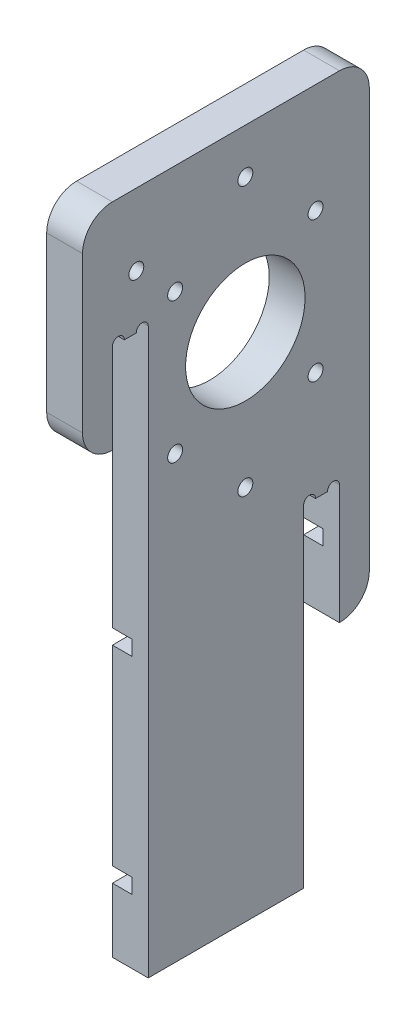
SolidWorks part; units mm, degrees
material "HDPE-green"
ref_plane "Front Plane" through (0, 0, 0) normal (0, 0, 1) x (1, 0, 0)
ref_plane "Top Plane" through (0, 0, 0) normal (0, 1, 0) x (1, 0, 0)
ref_plane "Right Plane" through (0, 0, 0) normal (1, 0, 0) x (0, 0, -1)
sketch "Sketch1" plane through (0, 0, 0) normal (1, 0, 0) x (0, 0, -1)
  line L1 (-31.5, 60) -> (31.5, 60)
  line L2 (-31.5, 60) -> (-31.5, -60)
  line L3 (-31.5, -60) -> (31.5, -60)
  line L4 (31.5, 60) -> (31.5, -60)
  line L5 (-31.5, 60) -> (31.5, -60) construction
  line L6 (-31.5, -60) -> (31.5, 60) construction
  circle A0 centre (0, 0) radius 20
  point P0 (0, 0)
  dimension "D3" = 40
  dimension "D1" = 63
  dimension "D2" = 120
extrude "Boss-Extrude1" add sketch "Sketch1" along normal blind 12
hole_wizard "Ø5.0 (5) Diameter Hole2" positions "Sketch5" profile "Sketch4" hole size "Ø5.0" standard "ISO" end condition up to next
sketch "Sketch5" plane through (0, 0, 0) normal (-1, 0, 0) x (0, 0, 1)
  point P0 (-23.5, 23.5)
  point P1 (23.5, 23.5)
  point P3 (23.5, -23.5)
  point P5 (-23.5, -23.5)
  dimension "D1" = 23.5
  dimension "D2" = 23.5
  dimension "D3" = 23.5
  dimension "D4" = 23.5
  dimension "D5" = 23.5
  dimension "D6" = 23.5
  dimension "D7" = 23.5
  dimension "D8" = 23.5
sketch "Sketch4" plane through (0, 23.5, -23.5) normal (0, 1, 0) x (0, 0, 1)
  line L0 (0, 0) -> (0, 12)
  line L1 (0, 12) -> (2.5, 12)
  line L2 (2.5, 12) -> (2.5, 0)
  line L5 (2.5, 0) -> (0, 0)
  line L11 (0, -6.35) -> (0, 107.95) construction
  dimension "Thru Hole Dia." = 5
  dimension "Thru Hole Depth" = 12
hole_wizard "Linear Rail Mount Hole" positions "Sketch7" profile "Sketch6" legacy end condition up to next
sketch "Sketch7" plane through (0, 0, 0) normal (-1, 0, 0) x (0, 0, 1)
  line L0 (0, -57.2998) -> (0, 35.7294) construction
  point P0 (0, 45)
  point P1 (0, -45)
  dimension "D1" = 45
  dimension "D2" = 45
sketch "Sketch6" plane through (0, 45, 0) normal (0, 1, 0) x (0, 0, 1)
  line L0 (0, 0) -> (0, 12)
  line L1 (0, 12) -> (2.5, 12)
  line L2 (2.5, 12) -> (2.5, 6)
  line L3 (2.5, 6) -> (6, 6)
  line L4 (6, 6) -> (6, 0)
  line L5 (6, 0) -> (0, 0)
  line L6 (0, 110) -> (0, -10) construction
  dimension "Diameter" = 5
  dimension "Depth" = 12
  dimension "C-Bore Diameter" = 12
  dimension "C-Bore Depth" = 6
sketch "Sketch8" plane through (0, 0, 0) normal (-1, 0, 0) x (0, 0, 1)
  line L2 (44.5, 18) -> (44.5, -12)
  line L3 (44.5, -12) -> (54.5, -12)
  line L4 (54.5, -12) -> (54.5, 60)
  line L5 (54.5, 60) -> (31.5, 60)
  line L7 (31.5, 60) -> (31.5, -60)
  line L9 (31.5, -60) -> (32.5, -60)
  line L10 (32.5, -60) -> (32.5, 18)
  line L11 (32.5, 18) -> (44.5, 18)
  dimension "D1" = 72
  dimension "D2" = 1
  dimension "D3" = 10
  dimension "D4" = 30
  dimension "D5" = 23
extrude "Boss-Extrude2" add sketch "Sketch8" against normal blind 12
sketch "Sketch9" plane through (0, 0, 0) normal (-1, 0, 0) x (0, 0, 1)
  line L0 (-31.5, -60) -> (-31.5, 60) construction
  line L1 (32.5, -60) -> (-19.5, -60)
  line L2 (32.5, -60) -> (32.5, -171)
  line L3 (32.5, -171) -> (-19.5, -171)
  line L4 (-19.5, -60) -> (-19.5, -171)
  dimension "D1" = 12
  dimension "D2" = 111
  dimension "D3" = 52
extrude "Boss-Extrude3" add sketch "Sketch9" against normal blind 12
sketch "Sketch11" plane through (12, 0, 0) normal (1, 0, 0) x (0, 0, -1)
  line L1 (31.5, 60) -> (41.5, 60)
  line L2 (31.5, 60) -> (31.5, -100)
  line L3 (31.5, -100) -> (41.5, -100)
  line L4 (41.5, 60) -> (41.5, -100)
  dimension "D1" = 10
  dimension "D2" = 160
extrude "Boss-Extrude4" add sketch "Sketch11" against normal blind 12
hole_wizard "Ø5.0 (5) Diameter Hole1" positions "Sketch22" profile "Sketch21" hole size "Ø5.0" standard "ISO" end condition up to next
sketch "Sketch22" plane through (12, 0, 0) normal (1, 0, 0) x (0, 0, -1)
  line L1 (41.5, 60) -> (-54.5, 60) construction
  line L2 (-32.5, -171) -> (-32.5, 18) construction
  point P0 (-36.5, 36)
  dimension "D1" = 4
  dimension "D2" = 24
sketch "Sketch21" plane through (12, 36, 36.5) normal (0, 1, 0) x (0, 0, -1)
  line L0 (0, 0) -> (0, 12)
  line L1 (0, 12) -> (2.5, 12)
  line L2 (2.5, 12) -> (2.5, 0)
  line L5 (2.5, 0) -> (0, 0)
  line L11 (0, -6.35) -> (0, 107.95) construction
  dimension "Thru Hole Dia." = 5
  dimension "Thru Hole Depth" = 12
fillet "Fillet1" radius 10 4 edges at (6, 60, 54.5) (6, -12, 54.5) (6, -100, -41.5) (6, 60, -41.5)
sketch "Sketch25" plane through (0, 0, 0) normal (-1, 0, 0) x (0, 0, 1)
  line L0 (32.5, 18) -> (44.5, 18) construction
  line L1 (-19.5, -60) -> (-31.5, -60) construction
  line L2 (32.5, 18) -> (36.5, 18)
  line L3 (40.5, 18) -> (44.5, 18)
  line L4 (-31.5, -60) -> (-27.5, -60)
  line L5 (-23.5, -60) -> (-19.5, -60)
  arc A0 (32.5, 18) -> (36.5, 18) centre (34.5, 18) cw
  arc A1 (44.5, 18) -> (40.5, 18) centre (42.5, 18) ccw
  arc A2 (-31.5, -60) -> (-27.5, -60) centre (-29.5, -60) cw
  arc A3 (-19.5, -60) -> (-23.5, -60) centre (-21.5, -60) ccw
  dimension "D1" = 2
  dimension "D2" = 2
  dimension "D3" = 2
  dimension "D4" = 2
extrude "Cut-Extrude1" cut sketch "Sketch25" against normal up to next
sketch "Sketch27" plane through (0, 35.2433, 16.6593) normal (-1, 0, 0) x (0, 0, 1)
  line L0 (3.8407, -178.2433) -> (3.8407, -186.2433) construction
  line L1 (5.8407, -178.2433) -> (5.8407, -186.2433)
  line L2 (1.8407, -178.2433) -> (1.8407, -186.2433)
  line L5 (-36.1593, -206.2433) -> (15.8407, -206.2433) construction
  line L6 (15.8407, -206.2433) -> (15.8407, -17.2433) construction
  arc A0 (5.8407, -178.2433) -> (1.8407, -178.2433) centre (3.8407, -178.2433) ccw
  arc A1 (1.8407, -186.2433) -> (5.8407, -186.2433) centre (3.8407, -186.2433) ccw
  point P2 (3.8407, -182.2433)
  dimension "D1" = 8
  dimension "D2" = 2
  dimension "D3" = 24
  dimension "D4" = 12
extrude "Cut-Extrude2" cut sketch "Sketch27" against normal blind 8
sketch "Sketch29" plane through (0, 35.2433, 16.6593) normal (-1, 0, 0) x (0, 0, 1)
  line L0 (61.7382, -182.2433) -> (-1.1593, -182.2433) construction
  line L1 (61.7382, -184.7433) -> (-1.1593, -184.7433)
  line L2 (61.7382, -179.7433) -> (-1.1593, -179.7433)
  line L5 (-36.1593, -206.2433) -> (15.8407, -206.2433) construction
  line L6 (15.8407, -206.2433) -> (15.8407, -17.2433) construction
  arc A0 (61.7382, -184.7433) -> (61.7382, -179.7433) centre (61.7382, -182.2433) ccw
  arc A1 (-1.1593, -179.7433) -> (-1.1593, -184.7433) centre (-1.1593, -182.2433) ccw
  point P2 (30.2895, -182.2433)
  dimension "D1" = 24
  dimension "D2" = 2.5
  dimension "D3" = 17
extrude "Cut-Extrude3" cut sketch "Sketch29" against normal blind 6.5
pattern_linear "LPattern1" count 2 spacing 69 along (0, 1, 0) of "Cut-Extrude2", "Cut-Extrude3"
ref_plane "Plane1" through (0, 0, 6.5) normal (0, 0, 1) x (1, 0, 0)
mirror "Mirror1" about plane through (0, 0, 6.5) normal (0, 0, 1) of "LPattern1", "Cut-Extrude2", "Cut-Extrude3"
